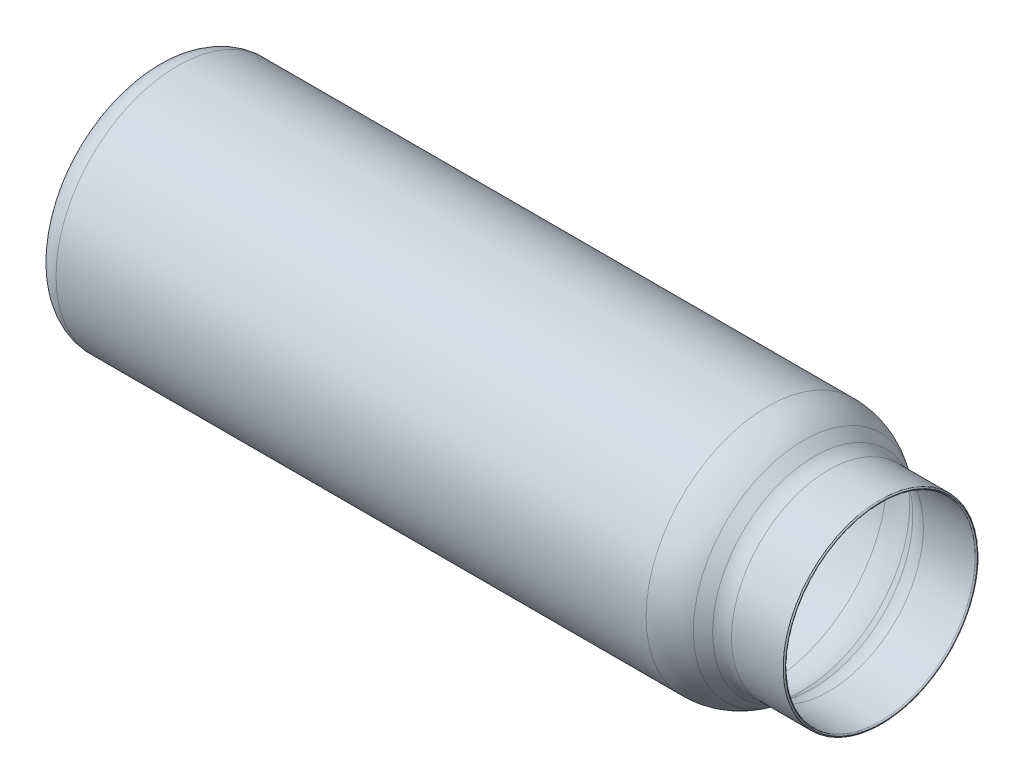
SolidWorks part; units mm, degrees
ref_plane "Front Plane" through (0, 0, 0) normal (0, 0, 1) x (1, 0, 0)
ref_plane "Top Plane" through (0, 0, 0) normal (0, 1, 0) x (1, 0, 0)
ref_plane "Right Plane" through (0, 0, 0) normal (1, 0, 0) x (0, 0, -1)
sketch "Sketch1" plane through (0, 0, 0) normal (0, 0, 1) x (1, 0, 0)
  line L0 (0, 0) -> (0, 74.3605) construction
  line L1 (0, 0) -> (-68.9746, 0) construction
  line L2 (-61.7247, 10) -> (-13.1689, 10)
  line L3 (-10.2323, 9.0468) -> (-9.3151, 8.3813)
  line L4 (-8.1405, 8) -> (-3.7897, 8)
  line L5 (-3.7897, 8) -> (-3.7897, 0)
  line L6 (-65.5929, 0) -> (-3.7897, 0)
  arc A0 (-63.718, 7.8355) -> (-63.3184, 0) centre (-188.2944, -2.4455) cw
  arc A1 (-13.1689, 10) -> (-10.2323, 9.0468) centre (-13.1689, 5) cw
  arc A2 (-8.1405, 8) -> (-9.3151, 8.3813) centre (-8.1405, 10) cw
  arc A3 (-63.718, 7.8355) -> (-61.7247, 10) centre (-61.7247, 8) cw
  point P13 (-11.5459, 10)
  point P17 (-61.5459, 10)
  point P22 (-8.7897, 8)
  dimension "D1" = 50
  dimension "D2" = 125
  dimension "D4" = 5
  dimension "D5" = 5
  dimension "D6" = 2
  dimension "D7" = 2
  dimension "D3" = 2
  dimension "D8" = 8
revolve "Revolve2" add sketch "Sketch1" angle 360 about L6 region at (-34.2072, 4.9094, 0)
shell "Shell2" thickness 0.2 removed face at (-3.7897, -8, 0)
fillet "Fillet5" radius 0.1 2 edges at (-3.7897, -8, 0) (-3.7897, 7.8, 0)
